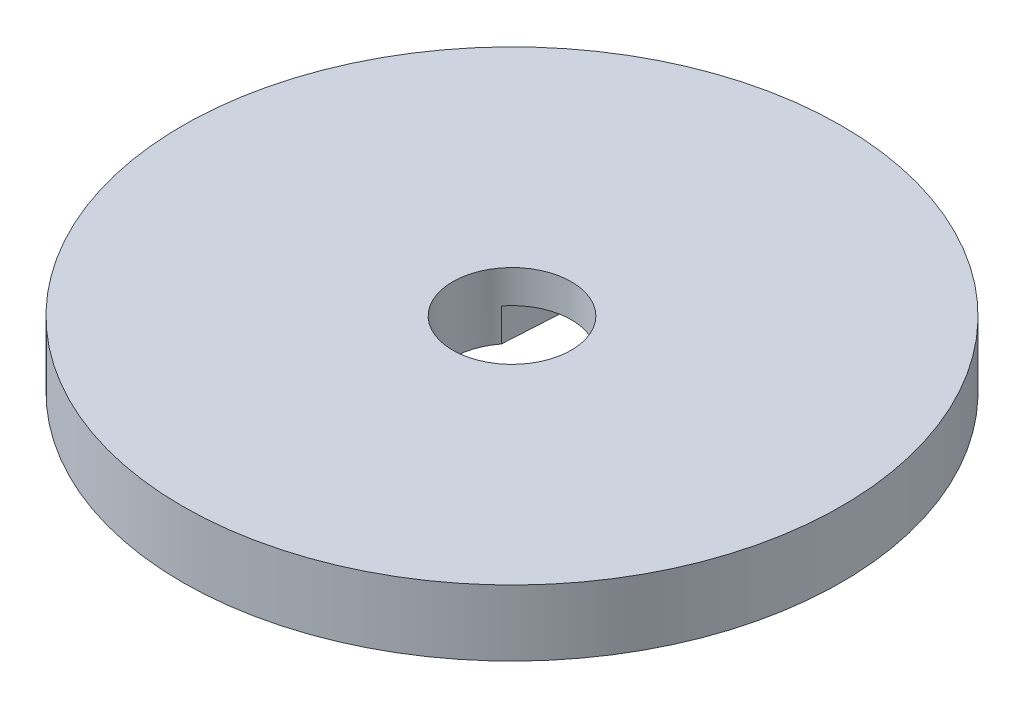
SolidWorks part; units mm, degrees
ref_plane "Front Plane" through (0, 0, 0) normal (0, 0, 1) x (1, 0, 0)
ref_plane "Top Plane" through (0, 0, 0) normal (0, 1, 0) x (1, 0, 0)
ref_plane "Right Plane" through (0, 0, 0) normal (1, 0, 0) x (0, 0, -1)
sketch "Sketch1" plane through (0, 0, 0) normal (0, 1, 0) x (1, 0, 0)
  line L0 (-2.75, -2.1651) -> (-1.9, -16.6)
  line L1 (1.9, -16.6) -> (2.75, -2.1651)
  line L2 (2.75, 2.1651) -> (1.9, 16.6)
  line L3 (-1.9, 16.6) -> (-2.75, 2.1651)
  line L4 (2.848, 2.202) -> (2, 16.603)
  line L5 (-2, 16.603) -> (-2.848, 2.202)
  line L6 (-2.848, -2.202) -> (-2, -16.603)
  line L7 (2, -16.603) -> (2.848, -2.202)
  arc A0 (-2.75, 2.1651) -> (-2.75, -2.1651) centre (0, 0) ccw
  arc A1 (-1.9, -16.6) -> (1.9, -16.6) centre (0, -16.6) ccw
  arc A2 (2.75, -2.1651) -> (3.5, 0) centre (0, 0) ccw
  arc A3 (3.5, 0) -> (2.75, 2.1651) centre (0, 0) ccw
  arc A4 (1.9, 16.6) -> (-1.9, 16.6) centre (0, 16.6) ccw
  arc A5 (2, 16.603) -> (-2, 16.603) centre (0, 16.6) ccw
  arc A6 (-2.848, 2.202) -> (-2.848, -2.202) centre (0, 0) ccw
  arc A7 (-2, -16.603) -> (2, -16.603) centre (0, -16.6) ccw
  arc A8 (2.848, -2.202) -> (3.6, 0) centre (0, 0) ccw
  arc A9 (3.6, 0) -> (2.848, 2.202) centre (0, 0) ccw
  circle A10 centre (0, 0) radius 20
  circle A11 centre (0, 0) radius 3.6
  dimension "D1" = 3.5
  dimension "D2" = 1.9
  dimension "D6" = 40
  dimension "D3" = 2.75
  dimension "D4" = 16.6
  dimension "D5" = 0.1
extrude "Boss-Extrude2" add sketch "Sketch1" along normal blind 4 contours A10 A9 A8 L7 A7 L6 A6 L5 A5 L4 | A11 L0 A1 L1 | A11 L2 A4 L3 | A11 L1 A1 L0 L6 A7 L7 | A11 L4 A5 L5 L3 A4 L2 region at (0, 0, 10.1891) region at (-2.3373, 0, 9.4685) region at (-2.8083, 0, -2.2801) region at (0, 0, -10.1891) region at (-19.4343, 0, 0)
extrude "Cut-Extrude2" cut sketch "Sketch1<6>" along normal blind 2 contours A11 L1 A1 L0 L6 A7 L7 | A11 L0 A1 L1 | A11 L2 A4 L3 | A11 L4 A5 L5 L3 A4 L2 region at (0, 0, 10.1891) region at (-2.3373, 0, 9.4685) region at (-2.8083, 0, -2.2801) region at (0, 0, -10.1891)
sketch "Sketch1<6>" plane through (0, 0, 0) normal (0, 1, 0) x (1, 0, 0) same geometry as "Sketch1"
